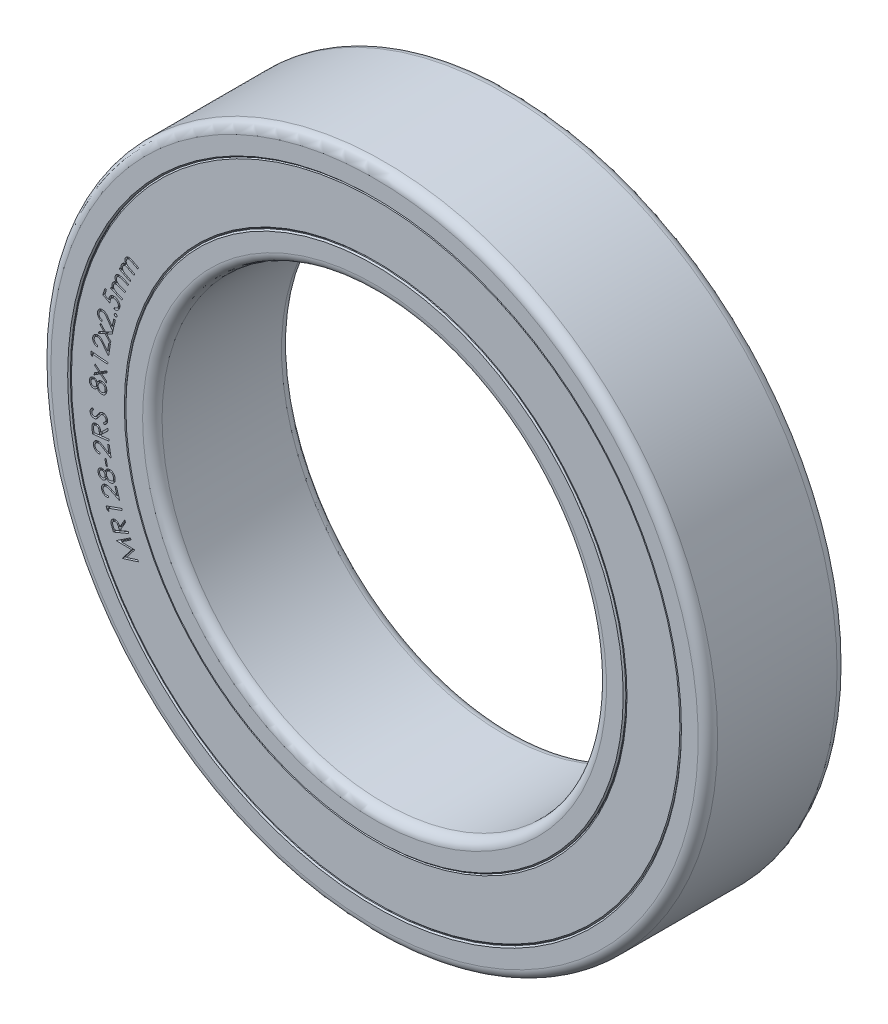
SolidWorks part; units mm, degrees
material "AISI 316 Annealed Stainless Steel Bar (SS)"
ref_plane "Front" through (0, 0, 0) normal (0, 0, 1) x (1, 0, 0)
ref_plane "Top" through (0, 0, 0) normal (0, 1, 0) x (1, 0, 0)
ref_plane "Right" through (0, 0, 0) normal (1, 0, 0) x (0, 0, -1)
sketch "LAYOUT R" plane through (0, 0, 0) normal (1, 0, 0) x (0, 0, -1)
  line L0 (-1.25, 4) -> (1.25, 4)
  line L1 (1.25, -6) -> (-1.25, -6) construction
  line L2 (1.25, -6) -> (1.25, 6) construction
  line L3 (1.25, 6) -> (-1.25, 6)
  line L4 (-1.25, -6) -> (-1.25, 6) construction
  line L5 (1.25, -6) -> (-1.25, 6) construction
  line L6 (1.25, 6) -> (-1.25, -6) construction
  line L7 (-1.25, 4.5) -> (1.25, 4.5)
  line L8 (-1.25, 5.5) -> (1.25, 5.5)
  line L11 (-17.5, 0) -> (17.5, 0) construction
  line L12 (-1.25, 6) -> (-1.25, 5.5)
  line L13 (1.25, 6) -> (1.25, 5.5)
  line L14 (-1.25, 5.5) -> (-1.25, 4.5)
  line L15 (1.25, 5.5) -> (1.25, 4.5)
  line L16 (-1.25, 4.5) -> (-1.25, 4)
  line L17 (1.25, 4.5) -> (1.25, 4)
  line L18 (-1.23, 5.5) -> (-1.23, 4.5)
  line L19 (1.23, 5.5) -> (1.23, 4.5)
  point P0 (0, 0)
  point P15 (0, 0)
  dimension "D1" = 2.5
  dimension "D2" = 12
  dimension "D3" = 4
  dimension "D6" = 0.02
  dimension "D7" = 0.02
  dimension "D4" = 4.5
  dimension "D5" = 5.5
sketch "Sketch R, INNER BODY" plane through (0, 0, 0) normal (1, 0, 0) x (0, 0, -1)
  line L0 (-1.25, 4) -> (1.25, 4) construction
  line L2 (-1.25, 4.5) -> (1.25, 4.5) construction
  line L4 (-1.25, 4) -> (1.25, 4)
  line L6 (-1.25, 4.5) -> (1.25, 4.5)
  line L8 (1.25, 4.5) -> (1.25, 4) construction
  line L9 (-1.25, 4.5) -> (-1.25, 4) construction
  line L10 (1.25, 4.5) -> (1.25, 4)
  line L11 (-1.25, 4.5) -> (-1.25, 4)
  line L12 (-17.5, 0) -> (17.5, 0) construction
  line L13 (-17.5, 0) -> (17.5, 0) construction
sketch "Sketch R, OUTER BODY" plane through (0, 0, 0) normal (1, 0, 0) x (0, 0, -1)
  line L2 (-1.25, 5.5) -> (1.25, 5.5) construction
  line L3 (1.25, 6) -> (-1.25, 6) construction
  line L6 (-1.25, 5.5) -> (1.25, 5.5)
  line L7 (1.25, 6) -> (-1.25, 6)
  line L8 (-17.5, 0) -> (17.5, 0) construction
  line L9 (-17.5, 0) -> (17.5, 0) construction
  line L10 (1.25, 6) -> (1.25, 5.5) construction
  line L11 (-1.25, 6) -> (-1.25, 5.5) construction
  line L12 (1.25, 6) -> (1.25, 5.5)
  line L13 (-1.25, 6) -> (-1.25, 5.5)
sketch "Sketch R, SEAL FACES" plane through (0, 0, 0) normal (1, 0, 0) x (0, 0, -1)
  line L0 (-17.5, 0) -> (17.5, 0) construction
  line L1 (-17.5, 0) -> (17.5, 0) construction
  line L3 (-1.25, 4.5) -> (1.25, 4.5) construction
  line L5 (-1.25, 5.5) -> (1.25, 5.5) construction
  line L7 (-1.23, 4.5) -> (1.23, 4.5)
  line L9 (-1.23, 5.5) -> (1.23, 5.5)
  line L10 (1.23, 5.5) -> (1.23, 4.5) construction
  line L11 (-1.23, 5.5) -> (-1.23, 4.5) construction
  line L12 (1.23, 5.5) -> (1.23, 4.5)
  line L13 (-1.23, 5.5) -> (-1.23, 4.5)
revolve "Revolve INNER BODY" add sketch "Sketch R, INNER BODY" angle 360 about L13
fillet "Fillet INNER BODY" radius 0.175 2 edges at (4, 0, 1.25) (4, 0, -1.25)
chamfer "Chamfer INNER BODY" distance 0.024 angle 45 2 edges at (4.5, 0, -1.25) (4.5, 0, 1.25)
revolve "Revolve OUTER BODY" add sketch "Sketch R, OUTER BODY" angle 360 about L9
fillet "Fillet OUTER BODY" radius 0.175 2 edges at (6, 0, -1.25) (6, 0, 1.25)
chamfer "Chamfer OUTER BODY" distance 0.024 angle 45 2 edges at (5.5, 0, 1.25) (5.5, 0, -1.25)
revolve "Revolve SEALS" add sketch "Sketch R, SEAL FACES" angle 360 about L1
chamfer "Chamfer SEALS" distance 0.024 angle 45 4 edges at (4.5, 0, -1.23) (5.5, 0, -1.23) (5.5, 0, 1.23) (4.5, 0, 1.23)
sketch "Sketch TEXT RADIUS 1 — MANUALLY ASSIGN TEXT AND FONT SIZE (FROM EQUATIONS)" plane through (0, 0, 1.23) normal (0, 0, 1) x (1, 0, 0)
  circle A0 centre (0, 0) radius 4.85 construction
  text T0 "MR128-2RS  8x12x2.5mm" font "Century Gothic" height 0.3
  dimension "D1" = 9.7
extrude "Cut-Extrude SEAL LABEL 1" cut sketch "Sketch TEXT RADIUS 1 — MANUALLY ASSIGN TEXT AND FONT SIZE (FROM EQUATIONS)" against normal blind 0.05
sketch "Sketch TEXT RADIUS 2 — MANUALLY ASSIGN TEXT AND FONT SIZE (FROM EQUATIONS)" plane through (0, 0, -1.23) normal (0, 0, -1) x (-1, 0, 0)
  circle A0 centre (0, 0) radius 4.85 construction
  text T0 "MR128-2RS  8x12x2.5mm" font "Century Gothic" height 0.3
  dimension "D1" = 9.7
extrude "Cut-Extrude SEAL LABEL 2" cut sketch "Sketch TEXT RADIUS 2 — MANUALLY ASSIGN TEXT AND FONT SIZE (FROM EQUATIONS)" against normal blind 0.05
equation "\"_i__BORE\"= 8"
equation "\"_i__OUTSIDE_DIAMETER\"= 12"
equation "\"_i__WIDTH\"= 2.5"
equation "\"_i_optional__TEXT_RADIUS_ADJUSTMENT\"= 0"
equation "\"_output__FONT_SIZE_mm\"= \"BODY_SPAN__SEAL__OF_RADIUS\" * \"param__FONT_SIZE_RATIO\"'MANUALLY ASSIGN TO FONT"
equation "\"BODY__HALF_WIDTH\"= \"_i__WIDTH\" / 2"
equation "\"BODY_SPAN___OF_DIAMETER\"= \"_i__OUTSIDE_DIAMETER\" - \"_i__BORE\""
equation "\"BODY_SPAN___OF_RADIUS\"= \"BODY_SPAN___OF_DIAMETER\" / 2"
equation "\"BODY_SPAN__BORE_AND_OD__OF RADIUS\"= ( \"BODY_SPAN___OF_RADIUS\" - \"BODY_SPAN__SEAL__OF_RADIUS\" ) / 2"
equation "\"BODY_SPAN__SEAL__OF_RADIUS\"= \"BODY_SPAN___OF_RADIUS\" * \"param__SEAL_PANEL_SPAN__RATIO_OF_BODY_RADIAN\""
equation "\"BORE__RADIUS\"= \"_i__BORE\" / 2"
equation "\"CORNER_RADII\"= \"_i__WIDTH\" * \"param__CORNER_RADII__ISO_MAX_RATIO_TO_WIDTH\""
equation "\"param__CORNER_RADII__ISO_MAX_RATIO_TO_WIDTH\"= 0.07'WHERE WIDTH IS LESS THAN DIAMETER"
equation "\"param__FONT_SIZE_RATIO\"= 0.3"
equation "\"param__SEAL_FACE_INSET__RATIO_OF_WIDTH\"= .01"
equation "\"param__SEAL_PANEL_SPAN__RATIO_OF_BODY_RADIAN\"= 0.5"
equation "\"param__SIDE_CHAMFERS__RATIO_TO_OD\"= 1 / 500"
equation "\"RING_INNER__OUTSIDE_RADIUS\"= \"BORE__RADIUS\" + \"BODY_SPAN__BORE_AND_OD__OF RADIUS\""
equation "\"RING_OUTER__OUTSIDE_RADIUS\"= ( \"_i__OUTSIDE_DIAMETER\" / 2 ) - \"BODY_SPAN__BORE_AND_OD__OF RADIUS\""
equation "\"SEAL_FACE_INSET\"= \"_i__WIDTH\" * \"param__SEAL_FACE_INSET__RATIO_OF_WIDTH\""
equation "\"SIDE_FACE_AND_SEAL_CHAMFERS\"= \"_i__OUTSIDE_DIAMETER\" * \"param__SIDE_CHAMFERS__RATIO_TO_OD\""
equation "\"TEXT_RADIUS\"= \"_i__BORE\" + ( \"BODY_SPAN___OF_DIAMETER\" / 2 ) - \"_output__FONT_SIZE_mm\" + \"_i_optional__TEXT_RADIUS_ADJUSTMENT\""
equation "\"D1@Chamfer INNER BODY\"=\"SIDE_FACE_AND_SEAL_CHAMFERS\""
equation "\"D1@Chamfer OUTER BODY\"=\"SIDE_FACE_AND_SEAL_CHAMFERS\""
equation "\"D1@Chamfer SEALS\"=\"SIDE_FACE_AND_SEAL_CHAMFERS\""
equation "\"D1@Fillet INNER BODY\"=\"CORNER_RADII\""
equation "\"D1@Fillet OUTER BODY\"=\"CORNER_RADII\""
equation "\"D1@LAYOUT R\"=\"_i__WIDTH\""
equation "\"D1@Sketch TEXT RADIUS 1 — MANUALLY ASSIGN TEXT AND FONT SIZE (FROM EQUATIONS)\" = \"TEXT_RADIUS\""
equation "\"D1@Sketch TEXT RADIUS 2 — MANUALLY ASSIGN TEXT AND FONT SIZE (FROM EQUATIONS)\" = \"TEXT_RADIUS\""
equation "\"D2@LAYOUT R\"=\"_i__OUTSIDE_DIAMETER\""
equation "\"D3@LAYOUT R\"=\"BORE__RADIUS\""
equation "\"D4@LAYOUT R\"=\"RING_INNER__OUTSIDE_RADIUS\""
equation "\"D5@LAYOUT R\"=\"RING_OUTER__OUTSIDE_RADIUS\""
